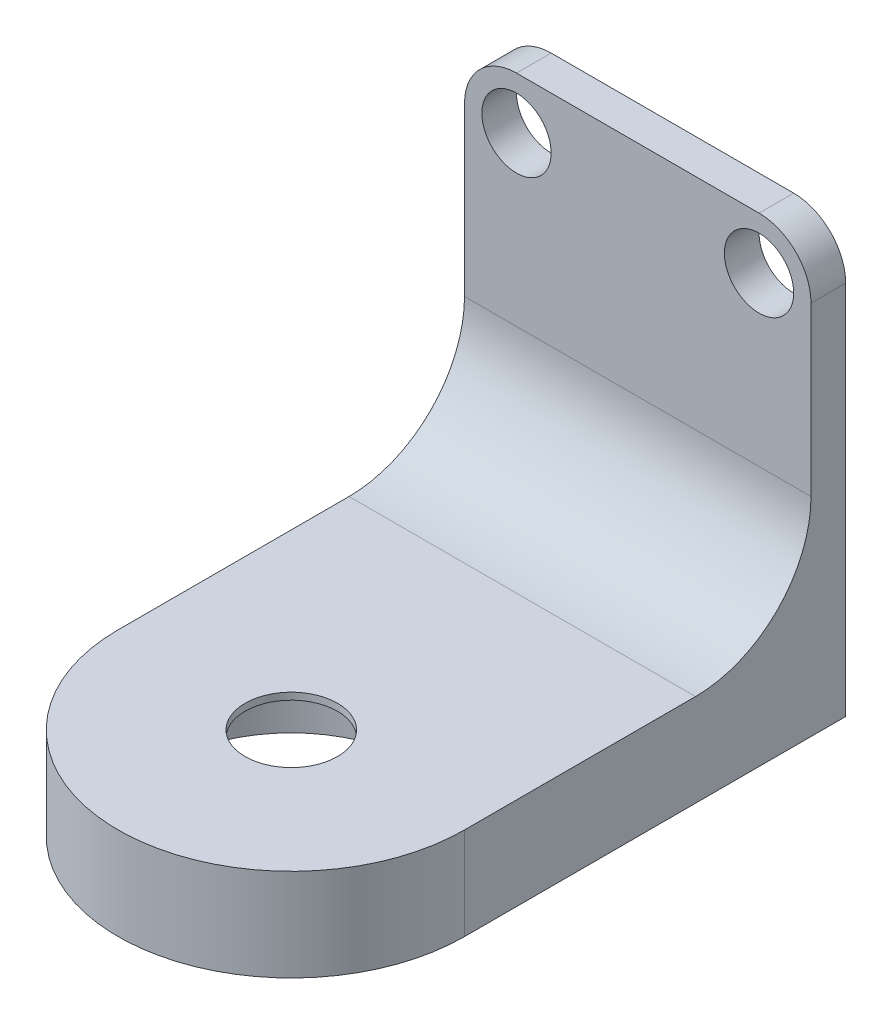
SolidWorks part; units mm, degrees
ref_plane "Front" through (0, 0, 0) normal (0, 0, 1) x (1, 0, 0)
ref_plane "Top" through (0, 0, 0) normal (0, 1, 0) x (1, 0, 0)
ref_plane "Right" through (0, 0, 0) normal (1, 0, 0) x (0, 0, -1)
sketch "草圖1" plane through (0, 0, 0) normal (0, 1, 0) x (1, 0, 0)
  line L0 (-15, 0) -> (-15, 30)
  line L1 (-15, 30) -> (15, 30)
  line L2 (15, 30) -> (15, 0)
  circle A0 centre (0, 0) radius 11
  arc A1 (-15, 0) -> (15, 0) centre (0, 0) ccw
  dimension "D1" = 22
  dimension "D2" = 15
  dimension "D3" = 30
extrude "填料-伸長1" add sketch "草圖1" along normal blind 8
sketch "草圖2" plane through (0, 0, -30) normal (0, 0, -1) x (-1, 0, 0)
  line L0 (0, -18.8885) -> (0, 18.8885) construction
  line L1 (-16.9222, 4) -> (16.9222, 4) construction
  line L2 (-10.5, 37) -> (10.5, 37)
  line L3 (-15, 32.5) -> (-15, 8)
  line L4 (-15, 8) -> (15, 8)
  line L5 (15, 32.5) -> (15, 8)
  line L6 (-15, 37) -> (15, 8) construction
  line L7 (-15, 8) -> (15, 37) construction
  line L8 (-15, 0) -> (15, 0)
  line L9 (-15, 0) -> (-15, 8)
  line L10 (-15, 8) -> (15, 8)
  line L11 (15, 0) -> (15, 8)
  line L12 (-15, 0) -> (15, 8) construction
  line L13 (-15, 8) -> (15, 0) construction
  circle A0 centre (-10.5, 4) radius 3
  circle A1 centre (10.5, 4) radius 3
  circle A2 centre (-10.5, 32.5) radius 3
  circle A3 centre (10.5, 32.5) radius 3
  arc A4 (-10.5, 37) -> (-15, 32.5) centre (-10.5, 32.5) ccw
  arc A5 (15, 32.5) -> (10.5, 37) centre (10.5, 32.5) ccw
  point P0 (0, 22.5)
  point P4 (0, 0)
  point P14 (0, 4)
  point P26 (0, 4)
  line M5 (-15, 0) -> (15, 0)
  line M6 (15, 0) -> (15, 8)
  line M7 (15, 8) -> (-15, 8)
  line M8 (-15, 8) -> (-15, 0)
  dimension "D4" = 6
  dimension "D6" = 4.5
  dimension "D1" = 21
  dimension "D3" = 28.5
  dimension "D5" = 4.5
  dimension "D2" = 2
extrude "填料-伸長2" add sketch "草圖2" along normal blind 3 contours A0 A1 M8 M5 M6 M7 | L5 A5 L2 A4 L3 A3 A2 M7 region at (0, 21.6516, -30) region at (0, 4, -30)
fillet "圓角1" radius 10 1 edges at (0, 8, -30)
extrude "填料-伸長3" add sketch "草圖1<2>" against normal blind 1 from surface contours A0 region at (0, 0, 0) starting at face at (0, 8, -6.25)
sketch "草圖1<2>" plane through (0, 0, 0) normal (0, 1, 0) x (1, 0, 0) same geometry as "草圖1"
sketch "草圖3" plane through (0, 7, 0) normal (0, -1, 0) x (-1, 0, 0)
  circle A0 centre (0, 0) radius 4
  dimension "D1" = 8
extrude "除料-伸長1" cut sketch "草圖3" against normal through all
sketch "草圖4" plane through (0, 7, 0) normal (0, -1, 0) x (-1, 0, 0)
  circle A0 centre (0, 0) radius 6.25
  dimension "D1" = 12.5
extrude "除料-伸長2" cut sketch "草圖4" against normal blind 0.4
